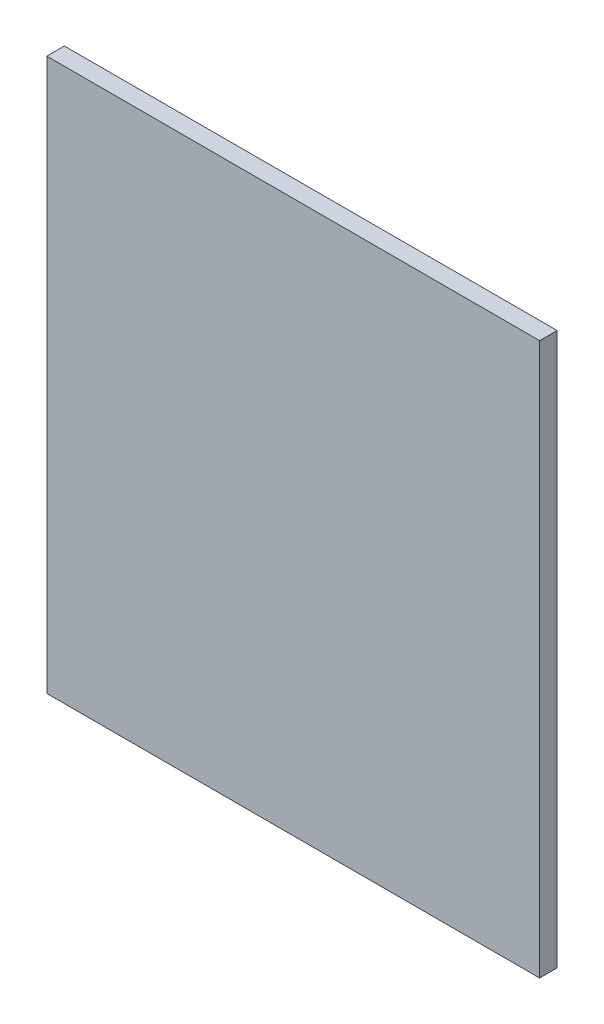
SolidWorks part; units mm, degrees
ref_plane "Front Plane" through (0, 0, 0) normal (0, 0, 1) x (1, 0, 0)
ref_plane "Top Plane" through (0, 0, 0) normal (0, 1, 0) x (1, 0, 0)
ref_plane "Right Plane" through (0, 0, 0) normal (1, 0, 0) x (0, 0, -1)
sketch "Sketch1" plane through (0, 0, 0) normal (0, 0, 1) x (1, 0, 0)
  line L0 (-44.645, 50) -> (-14.8817, 50)
  line L1 (-44.645, -50) -> (44.645, -50)
  line L2 (-44.645, -50) -> (-44.645, 50)
  line L3 (-44.645, 50) -> (44.645, 50) construction
  line L4 (44.645, -50) -> (44.645, 50)
  line L5 (-44.645, -50) -> (44.645, 50) construction
  line L6 (-44.645, 50) -> (44.645, -50) construction
  line L7 (-14.8817, 50) -> (14.8817, 50)
  line L8 (14.8817, 50) -> (44.645, 50)
  point P0 (0, 0)
  dimension "D1" = 89.29
  dimension "D2" = 100
extrude "Boss-Extrude1" add sketch "Sketch1" along normal blind 3.18
